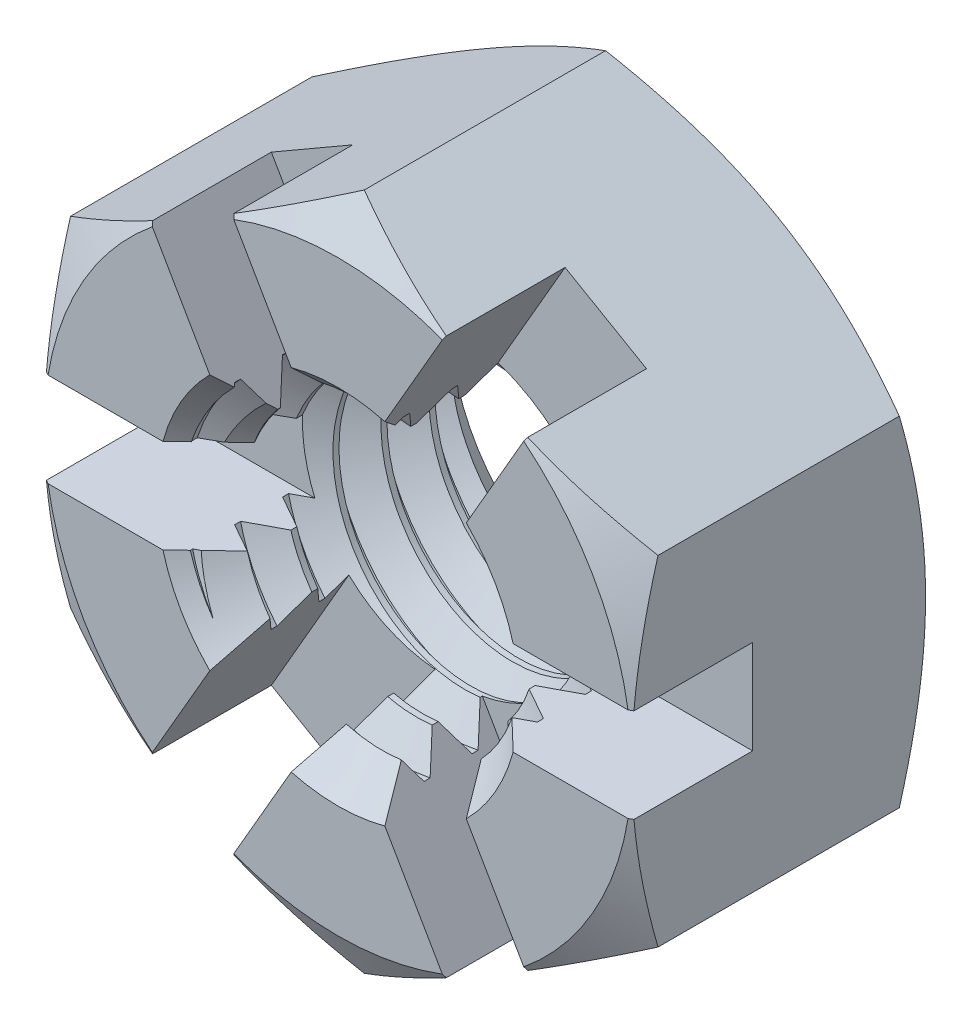
SolidWorks part; units mm, degrees
ref_plane "Front Plane" through (0, 0, 0) normal (0, 0, 1) x (1, 0, 0)
ref_plane "Top Plane" through (0, 0, 0) normal (0, 1, 0) x (1, 0, 0)
ref_plane "Right Plane" through (0, 0, 0) normal (1, 0, 0) x (0, 0, -1)
sketch "Sketch1" plane through (0, 0, 0) normal (0, 0, 1) x (1, 0, 0)
  line L1 (0, 6.4158) -> (-5.5563, 3.2079)
  line L2 (-5.5563, 3.2079) -> (-5.5563, -3.2079)
  line L3 (-5.5563, -3.2079) -> (0, -6.4158)
  line L4 (0, -6.4158) -> (5.5562, -3.2079)
  line L5 (5.5562, -3.2079) -> (5.5562, 3.2079)
  line L6 (5.5562, 3.2079) -> (0, 6.4158)
  circle A0 centre (0, 0) radius 5.5563 construction
  dimension "Hex" = 11.1125
extrude "Extrude1" add sketch "Sketch1" against normal blind 5.5562
sketch "Sketch2" plane through (0, 0, 0) normal (0, 0, 1) x (1, 0, 0)
  circle A0 centre (0, 0) radius 5.5563 construction
  circle A1 centre (0, 0) radius 5.5563
extrude "Cut-Extrude1" cut sketch "Sketch2" against normal through all draft 60 flip side to cut
sketch "Sketch3" plane through (0, 0, -5.5562) normal (0, 0, -1) x (-1, 0, 0)
  circle A1 centre (0, 0) radius 5.5563
  circle A2 centre (0, 0) radius 5.5563
  dimension "D1" = 0
extrude "Cut-Extrude2" cut sketch "Sketch3" against normal through all draft 60 flip side to cut
sketch "Sketch4" plane through (0, 0, 0) normal (0, 0, 1) x (1, 0, 0)
  circle A0 centre (0, 0) radius 3.175
  dimension "Thread Dia" = 6.35
extrude "Cut-Extrude3" cut sketch "Sketch4" against normal through all
sketch "Sketch7" plane through (0, 0, 0) normal (0, 0, 1) x (1, 0, 0)
  circle A4 centre (0, 0) radius 3.429
  circle A5 centre (0, 0) radius 3.429
  dimension "D1" = 0.254
sketch "Sketch8" plane through (0, 0, -5.5562) normal (0, 0, -1) x (-1, 0, 0)
  circle A1 centre (0, 0) radius 3.429
  circle A2 centre (0, 0) radius 3.429 construction
sketch "Sketch5" plane through (0, 0, 0) normal (0, 0, 1) x (1, 0, 0)
  circle A0 centre (0, 0) radius 3.175 construction
  circle A1 centre (0, 0) radius 3.175
curve "Helix/Spiral1" pitch 0.9071 height 6.4634 turns 7.125 parameters "pitch"=0.9071
sketch "Sketch9" plane through (0, 0, 0) normal (1, 0, 0) x (0, 0, -1)
  line L0 (-0.4536, 3.175) -> (-0.3402, 3.175)
  line L1 (-0.3402, 3.175) -> (0, 2.5858)
  line L2 (-0.4536, 3.175) -> (-0.7937, 2.5858)
  line L3 (-0.7937, 2.5858) -> (0, 2.5858)
  line L4 (-0.3969, 3.175) -> (-0.3969, 2.5858) construction
  line L5 (-0.6237, 2.8804) -> (-0.1701, 2.8804) construction
  line L7 (0, 2.5858) -> (0, 3.175) construction
  line L8 (0, 3.175) -> (0, -3.175) construction
  dimension "D1" = 0.1134
  dimension "D2" = 0.4536
  dimension "D3" = 60
sketch "Sketch12" plane through (0, 0, 0) normal (0, 0, 1) x (1, 0, 0)
  circle A0 centre (0, 0) radius 2.5858
  circle A1 centre (0, 0) radius 3.175 construction
  circle A2 centre (0, 0) radius 3.175
extrude "Extrude2" add sketch "Sketch12" against normal up to surface (5.5562 mm away) up to face at (3.175, 0, -5.5562)
sweep "Cut-Sweep1" cut profiles "Sketch9" path "Helix/Spiral1"
extrude "Cut-Extrude6" cut sketch "Sketch7" against normal through all draft 45
extrude "Cut-Extrude7" cut sketch "Sketch8" against normal through all draft 45
sketch "Sketch13" plane through (0, 0, 0) normal (0, 0, 1) x (1, 0, 0)
  line L0 (-0.7699, 0.4445) -> (0.7699, -0.4445)
  line L1 (-0.7699, 0.4445) -> (2.0082, 5.2564)
  line L2 (0.7699, -0.4445) -> (3.548, 4.3674)
  line L3 (2.0082, 5.2564) -> (3.548, 4.3674)
  line L4 (5.5562, 3.2079) -> (2.7781, 4.8119) construction
  dimension "slot width" = 1.778
extrude "Cut-Extrude8" cut sketch "Sketch13" against normal blind 2.286
pattern_circular "CirPattern1" count 6 over 360 about axis through (0, 0, 0) along (0, 0, 1) of "Cut-Extrude8"
equation "\"D2@Sketch9\" = \"pitch@Helix/Spiral1\"*.5"
equation "\"D3@Helix/Spiral1\" = \"pitch@Helix/Spiral1\"+\"Height@Extrude1\""
equation "\"D1@Sketch9\" = \"pitch@Helix/Spiral1\"*.125"
